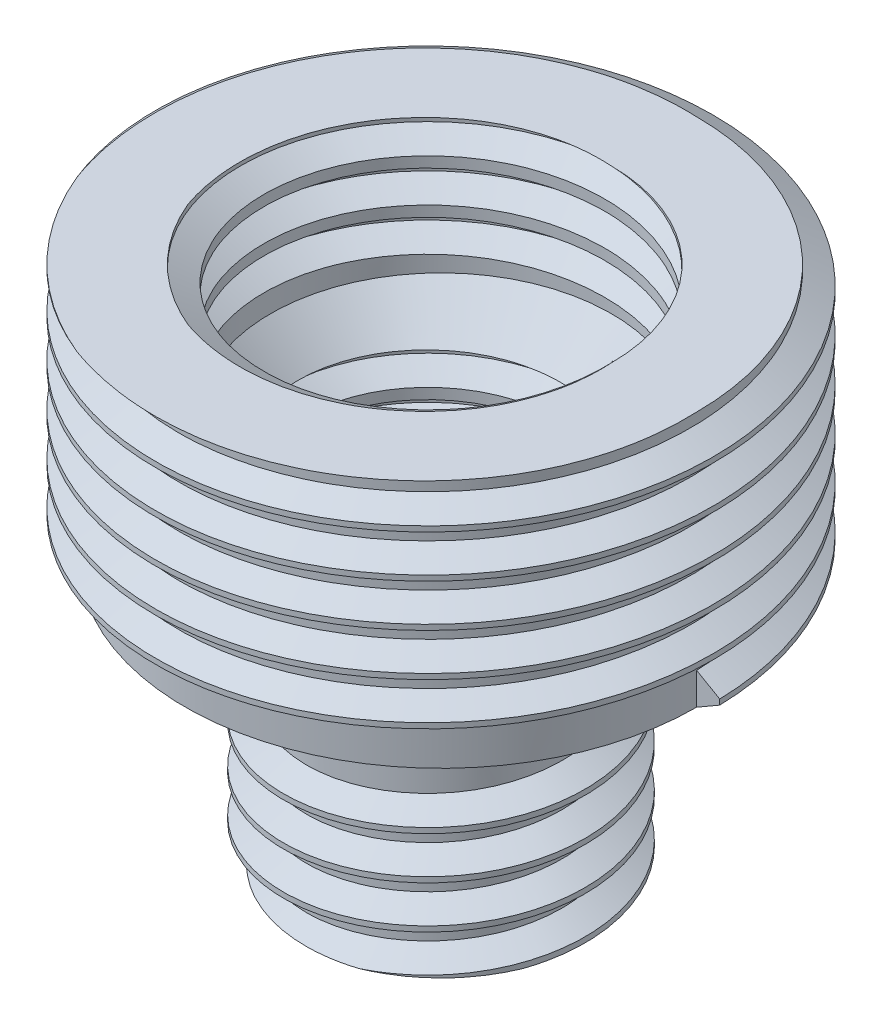
SolidWorks part; units mm, degrees
ref_plane "Front Plane" through (0, 0, 0) normal (0, 0, 1) x (1, 0, 0)
ref_plane "Top Plane" through (0, 0, 0) normal (0, 1, 0) x (1, 0, 0)
ref_plane "Right Plane" through (0, 0, 0) normal (1, 0, 0) x (0, 0, -1)
sketch "Sketch1" plane through (0, 0, 0) normal (0, 0, 1) x (1, 0, 0)
  line L0 (-4, 1.5) -> (-6, 1.5)
  line L1 (-4, 1.5) -> (4, 1.5) construction
  line L2 (-4, 1.5) -> (-4, -1.5) construction
  line L3 (-4, -1.5) -> (4, -1.5) construction
  line L4 (4, 1.5) -> (4, -1.5) construction
  line L5 (-4, 1.5) -> (4, -1.5) construction
  line L6 (-4, -1.5) -> (4, 1.5) construction
  line L7 (-3, -4.5) -> (3, -4.5) construction
  line L8 (-3, -4.5) -> (-3, -1.5) construction
  line L9 (-3, -1.5) -> (3, -1.5) construction
  line L10 (3, -4.5) -> (3, -1.5) construction
  line L11 (-3, -4.5) -> (3, -1.5) construction
  line L12 (-3, -1.5) -> (3, -4.5) construction
  line L13 (-3, -4.5) -> (3, -4.5) construction
  line L14 (-3, -4.5) -> (-3, -10.5) construction
  line L15 (-3, -10.5) -> (3, -10.5) construction
  line L16 (3, -4.5) -> (3, -10.5) construction
  line L17 (-3, -4.5) -> (3, -10.5) construction
  line L18 (-3, -10.5) -> (3, -4.5) construction
  line L19 (-6, -4.5) -> (6, -4.5) construction
  line L20 (-6, -4.5) -> (-6, 1.5) construction
  line L21 (-6, 1.5) -> (6, 1.5) construction
  line L22 (6, -4.5) -> (6, 1.5) construction
  line L23 (-6, -4.5) -> (6, 1.5) construction
  line L24 (-6, 1.5) -> (6, -4.5) construction
  line L25 (-6, 1.5) -> (-6, -4.5)
  line L26 (-6, -4.5) -> (-3, -6.5)
  line L27 (-3, -6.5) -> (-3, -10.5)
  line L28 (-3, -10.5) -> (-1.25, -10.5)
  line L31 (-3, -4.5) -> (-3, -2.5)
  line L32 (-3, -2.5) -> (-4, -1.5)
  line L33 (-4, -1.5) -> (-4, 1.5)
  line L34 (-3, -4.5) -> (-1.25, -6.25)
  line L35 (-1.25, -6.25) -> (-1.25, -10.5)
  line L36 (0, -10.5) -> (0, 1.5) construction
  line L37 (-1.25, -10.5) -> (1.25, -10.5) construction
  line L38 (-1.25, -10.5) -> (-1.25, -4.5) construction
  line L39 (-1.25, -4.5) -> (1.25, -4.5) construction
  line L40 (1.25, -10.5) -> (1.25, -4.5) construction
  line L41 (-1.25, -10.5) -> (1.25, -4.5) construction
  line L42 (-1.25, -4.5) -> (1.25, -10.5) construction
  point P0 (0, 0)
  point P6 (0, -3)
  point P11 (0, -7.5)
  point P16 (0, -1.5)
  point P23 (0, -7.5)
  dimension "D1" = 8
  dimension "D2" = 3
  dimension "D3" = 3
  dimension "D4" = 6
  dimension "D5" = 12
  dimension "D6" = 6
  dimension "D7" = 6
  dimension "D8" = 6
  dimension "D9" = 1
  dimension "D10" = 2
  dimension "D11" = 2.5
  dimension "D12" = 45
revolve "Revolve1" add sketch "Sketch1" angle 360 about L36
thread "Thread1" pitch 1 method cut profile "Thread Profile1" start angle 0, offset 0, length 0, pitch 1, diameter 8
ref_plane "Plane1" through (4, -1.5, 0) normal (0, 0, 1) x (1, 0, 0)
sketch "Thread Profile1" plane through (4, -1.5, 0) normal (0, 0, 1) x (1, 0, 0)
  line L0 (0, 0) -> (0, 1) construction
  line L1 (0, 0) -> (0.5413, 0.3125)
  line L2 (0.5413, 0.3125) -> (0.5413, 0.4375)
  line L3 (0.5413, 0.4375) -> (0, 0.75)
  line L4 (0.5413, 0.375) -> (0, 0.375) construction
  line L11 (0, 0) -> (0, 0.75)
  point P2 (0, 0)
  dimension "Pitch" = 1
  dimension "Profile_Angle" = 60
  dimension "Profile_Land" = 0.125
  dimension "Profile_Height" = 0.5413
thread "Thread2" pitch 1 method cut profile "Thread Profile2" start angle 0, offset 0, length 0, pitch 1, diameter 6
ref_plane "Plane2" through (3, -4.5, 0) normal (0, 0, 1) x (1, 0, 0)
sketch "Thread Profile2" plane through (3, -4.5, 0) normal (0, 0, 1) x (1, 0, 0)
  line L0 (0, 0) -> (0, 1) construction
  line L1 (0, 0) -> (0.5413, 0.3125)
  line L2 (0.5413, 0.3125) -> (0.5413, 0.4375)
  line L3 (0.5413, 0.4375) -> (0, 0.75)
  line L4 (0.5413, 0.375) -> (0, 0.375) construction
  line L11 (0, 0) -> (0, 0.75)
  point P2 (0, 0)
  dimension "Pitch" = 1
  dimension "Profile_Angle" = 60
  dimension "Profile_Land" = 0.125
  dimension "Profile_Height" = 0.5413
thread "Thread3" pitch 1 method extrude profile "Thread Profile3" start angle 0, offset 0, length 0, pitch 1, diameter 12
ref_plane "Plane3" through (6, -4.5, 0) normal (0, 0, 1) x (1, 0, 0)
sketch "Thread Profile3" plane through (6, -4.5, 0) normal (0, 0, 1) x (1, 0, 0)
  line L0 (0, 0) -> (0, 1) construction
  line L1 (0, 0) -> (0.5413, 0.3125)
  line L2 (0.5413, 0.3125) -> (0.5413, 0.4375)
  line L3 (0.5413, 0.4375) -> (0, 0.75)
  line L4 (0.5413, 0.375) -> (0, 0.375) construction
  line L11 (0, 0) -> (0, 0.75)
  point P2 (0, 0)
  dimension "Pitch" = 1
  dimension "Profile_Angle" = 60
  dimension "Profile_Land" = 0.125
  dimension "Profile_Height" = 0.5413
sketch "Sketch8" plane through (0, 1.5, 0) normal (0, 1, 0) x (1, 0, 0)
  circle A0 centre (0, 0) radius 12.5
  dimension "D1" = 25
extrude "Cut-Extrude1" cut sketch "Sketch8" along normal through all
thread "Thread4" pitch 1 method extrude profile "Thread Profile4" start angle 0, offset 0, length 0, pitch 1, diameter 6
ref_plane "Plane4" through (-3, -6.5, 0) normal (0, 0, 1) x (-1, 0, 0)
sketch "Thread Profile4" plane through (-3, -6.5, 0) normal (0, 0, 1) x (-1, 0, 0)
  line L0 (0, 0) -> (0, 1) construction
  line L1 (0, 0) -> (0.5413, 0.3125)
  line L2 (0.5413, 0.3125) -> (0.5413, 0.4375)
  line L3 (0.5413, 0.4375) -> (0, 0.75)
  line L4 (0.5413, 0.375) -> (0, 0.375) construction
  line L11 (0, 0) -> (0, 0.75)
  point P2 (0, 0)
  dimension "Pitch" = 1
  dimension "Profile_Angle" = 60
  dimension "Profile_Land" = 0.125
  dimension "Profile_Height" = 0.5413
sketch "Sketch11" plane through (0, -10.5, 0) normal (0, -1, 0) x (1, 0, 0)
  circle A0 centre (0, 0) radius 7.5
  dimension "D1" = 15
extrude "Cut-Extrude2" cut sketch "Sketch11" along normal through all
